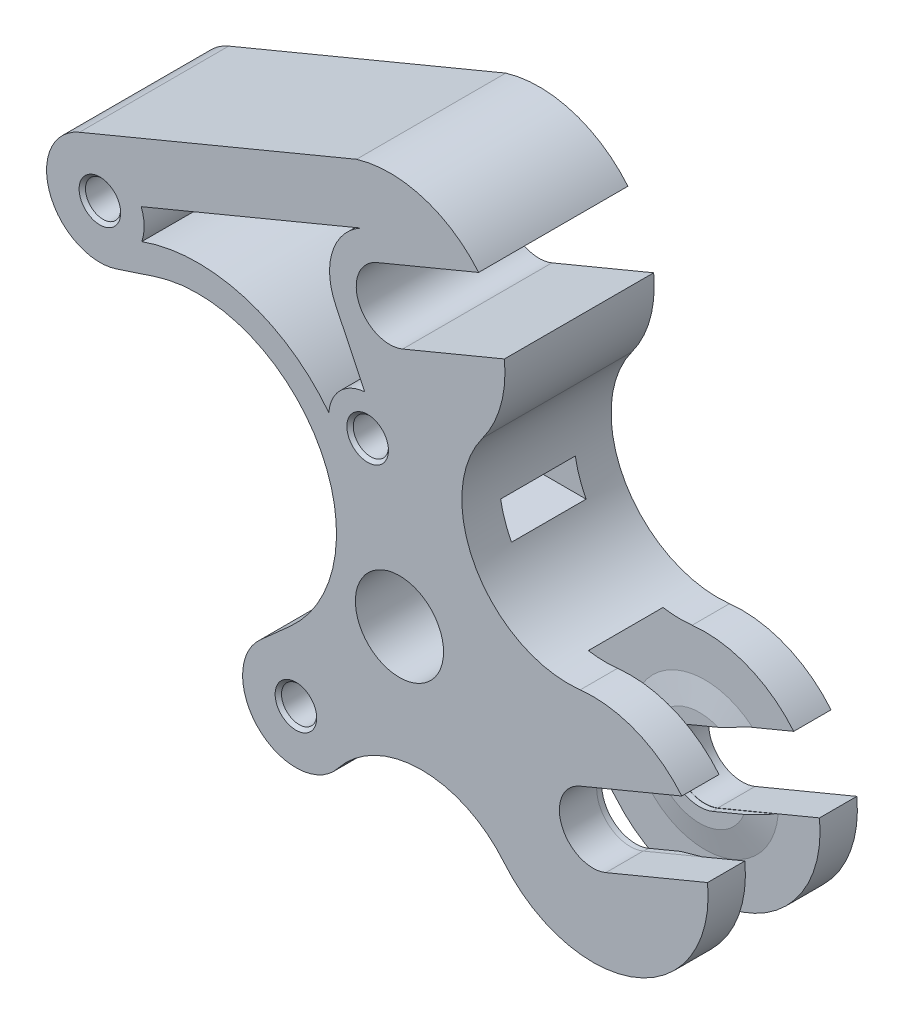
SolidWorks part; units mm, degrees
ref_plane "Front Plane" through (0, 0, 0) normal (0, 0, 1) x (1, 0, 0)
ref_plane "Top Plane" through (0, 0, 0) normal (0, 1, 0) x (1, 0, 0)
ref_plane "Right Plane" through (0, 0, 0) normal (1, 0, 0) x (0, 0, -1)
ref_plane "Plane1" through (0, 0, 7) normal (0, 0, 1) x (1, 0, 0)
sketch "Sketch1" plane through (0, 0, 0) normal (0, 0, 1) x (1, 0, 0)
  line L0 (18, 21) -> (37.0525, -11.9999) construction
  line L1 (15.9217, 9.1924) -> (-9.1924, 15.9217) construction
  line L2 (-9.1924, 15.9217) -> (-15.9217, -9.1924) construction
  line L3 (-15.9217, -9.1924) -> (9.1924, -15.9217) construction
  line L4 (9.1924, -15.9217) -> (15.9217, 9.1924) construction
  line L5 (0, 0) -> (50.7667, 0) construction
  line L6 (0, 0) -> (-9.1924, 15.9217) construction
  line L7 (-4.0727, 12.3456) -> (-7.626, 11.1734)
  line L8 (8.6552, -9.6998) -> (5.8634, -12.191)
  line L9 (0, 0) -> (9.1924, -15.9217) construction
  line L10 (14.8777, 31.3388) -> (-11.1111, 20.5389)
  line L11 (16.7912, 23.9088) -> (26.3307, 27.8731)
  line L12 (19.2088, 18.0912) -> (28.7483, 22.0554)
  line L13 (35.8437, -9.0911) -> (45.3832, -5.1268)
  line L14 (38.2613, -14.9087) -> (47.8008, -10.9445)
  arc A0 (8.6552, -9.6998) -> (-4.0727, 12.3456) centre (0, 0) ccw
  arc A1 (16.7912, 23.9088) -> (19.2088, 18.0912) centre (18, 21) ccw
  circle A2 centre (-9.1924, 15.9217) radius 1.65
  circle A3 centre (15.9217, 9.1924) radius 1.65
  circle A4 centre (9.1924, -15.9217) radius 1.65
  arc A5 (26.6989, 14.5993) -> (28.7483, 22.0554) centre (18, 21) ccw
  arc A6 (35.8437, -9.0911) -> (38.2613, -14.9087) centre (37.0525, -11.9999) ccw
  arc A7 (-11.1111, 20.5389) -> (-7.626, 11.1734) centre (-9.1924, 15.9217) ccw
  arc A8 (45.3832, -5.1268) -> (35.8587, -1.2661) centre (37.0525, -11.9999) ccw
  arc A9 (28.7062, -18.854) -> (47.8008, -10.9445) centre (37.0525, -11.9999) ccw
  arc A10 (5.8634, -12.191) -> (13.121, -19.0146) centre (9.1924, -15.9217) ccw
  arc A11 (28.7062, -18.854) -> (13.121, -19.0146) centre (20.9781, -25.2005) ccw
  arc A12 (26.6989, 14.5993) -> (35.8587, -1.2661) centre (34.7534, 8.6726) ccw
  arc A13 (26.3307, 27.8731) -> (14.8777, 31.3388) centre (18, 21) ccw
  dimension "D1" = 26
  dimension "D2" = 3.3
  dimension "D3" = 6.3
  dimension "D9" = 5
  dimension "D10" = 10.8
  dimension "D11" = 10
  dimension "D12" = 10
  dimension "D4" = 21
  dimension "D5" = 38.105
  dimension "D6" = 60
  dimension "D7" = 18
  dimension "D8" = 15
extrude "Boss-Extrude1" add sketch "Sketch1" along normal blind 14
sketch "Sketch3" plane through (0, 0, 7) normal (0, 0, 1) x (1, 0, 0)
  line L0 (0, 7) -> (37.0525, 7)
  line L1 (-2.9117, -6.3657) -> (32.2689, -22.4578)
  line L2 (5.7446, 4) -> (37.0525, 4)
  line L3 (3.5601, -6.0271) -> (26.4728, -16.5076)
  line L4 (37.0525, 4) -> (37.0525, 7)
  line L5 (0, 4) -> (23.3288, 4) construction
  line L6 (-1.6639, -3.6375) -> (33.5168, -19.7296) construction
  line L7 (0, 7) -> (23.3288, 7) construction
  circle A0 centre (37.0525, -11.9999) radius 9.5 construction
  arc A1 (32.2689, -22.4578) -> (26.4728, -16.5076) centre (37.0525, -11.9999) ccw
  arc A2 (35.8437, -9.0911) -> (38.2613, -14.9087) centre (37.0525, -11.9999) ccw construction
  circle A3 centre (0, 0) radius 5 construction
  arc A4 (0, 7) -> (-2.9117, -6.3657) centre (0, 0) ccw
  arc A6 (3.5601, -6.0271) -> (5.7446, 4) centre (0, 0) ccw
  dimension "D1" = 19
  dimension "D2" = 2
  dimension "D3" = 10
  dimension "D4" = 2
  dimension "D5" = 3
  dimension "D6" = 3
extrude "Cut-Extrude1" cut sketch "Sketch3" against normal blind 3.5 and the other way blind 3.5
sketch "Sketch4" plane through (0, 0, 14) normal (0, 0, 1) x (1, 0, 0)
  line L0 (15.6386, 12.8314) -> (12.9012, 18.566)
  line L1 (14.8777, 31.3388) -> (-11.1111, 20.5389) construction
  line L5 (15.2925, 25.959) -> (-5.3131, 17.3961)
  circle A0 centre (18.906, -4.6018) radius 4.1348
  arc A1 (12.2812, 9.4563) -> (-5.2659, 14.5781) centre (0, 0) ccw
  arc A2 (15.6386, 12.8314) -> (12.2812, 9.4563) centre (15.9217, 9.1924) ccw
  arc A3 (15.2925, 25.959) -> (12.9012, 18.566) centre (18, 21) ccw
  arc A4 (-5.2659, 14.5781) -> (-5.3131, 17.3961) centre (-9.1924, 15.9217) ccw
  arc A5 (16.7912, 23.9088) -> (19.2088, 18.0912) centre (18, 21) ccw construction
  arc A6 (8.6552, -9.6998) -> (-4.0727, 12.3456) centre (0, 0) ccw construction
  circle A7 centre (15.9217, 9.1924) radius 1.65 construction
  circle A8 centre (-9.1924, 15.9217) radius 1.65 construction
  dimension "D1" = 2.5
  dimension "D2" = 2.5
  dimension "D3" = 2
  dimension "D4" = 2.5
extrude "Cut-Extrude2" cut sketch "Sketch4" against normal through all
sketch "Sketch5" plane through (0, 0, 3.5) normal (0, 0, 1) x (1, 0, 0)
  line L0 (35.8356, -9.0715) -> (38.7839, -7.8463)
  line L1 (38.2694, -14.9283) -> (41.2177, -13.7031)
  line L2 (47.8008, -10.9445) -> (38.2613, -14.9087) construction
  line L3 (35.8437, -9.0911) -> (45.3832, -5.1268) construction
  line L7 (37.0525, -11.9999) -> (43.022, -20.3936) construction
  line L8 (37.0525, -11.9999) -> (32.7681, -21.3665) construction
  arc A0 (35.8356, -9.0715) -> (38.2694, -14.9283) centre (37.0525, -11.9999) ccw
  arc A1 (38.7839, -7.8463) -> (41.2177, -13.7031) centre (37.0525, -11.9999) ccw
  dimension "D1" = 4.5
extrude "Boss-Extrude2" add sketch "Sketch5" along normal blind 0.5
chamfer "Chamfer1" distance 2.4 distance2 0.5 1 edges at (32.897, -13.7268, 3.5) first distance on face at (27.688, -10.596, 3.5)
mirror "Mirror2" about plane through (0, 0, 7) normal (0, 0, 1) of "Boss-Extrude2"
chamfer "Chamfer3" distance 0.5 distance2 2.4 1 edges at (32.897, -13.7268, 10.5) first distance on face at (36.4489, -12.2507, 10.25)
chamfer "Chamfer4" distance 0.3 angle 45 6 edges at (10.8424, -15.9217, 0) (17.5717, 9.1924, 0) (-7.5424, 15.9217, 0) (10.8424, -15.9217, 14) (17.5717, 9.1924, 14) (-7.5424, 15.9217, 14)
